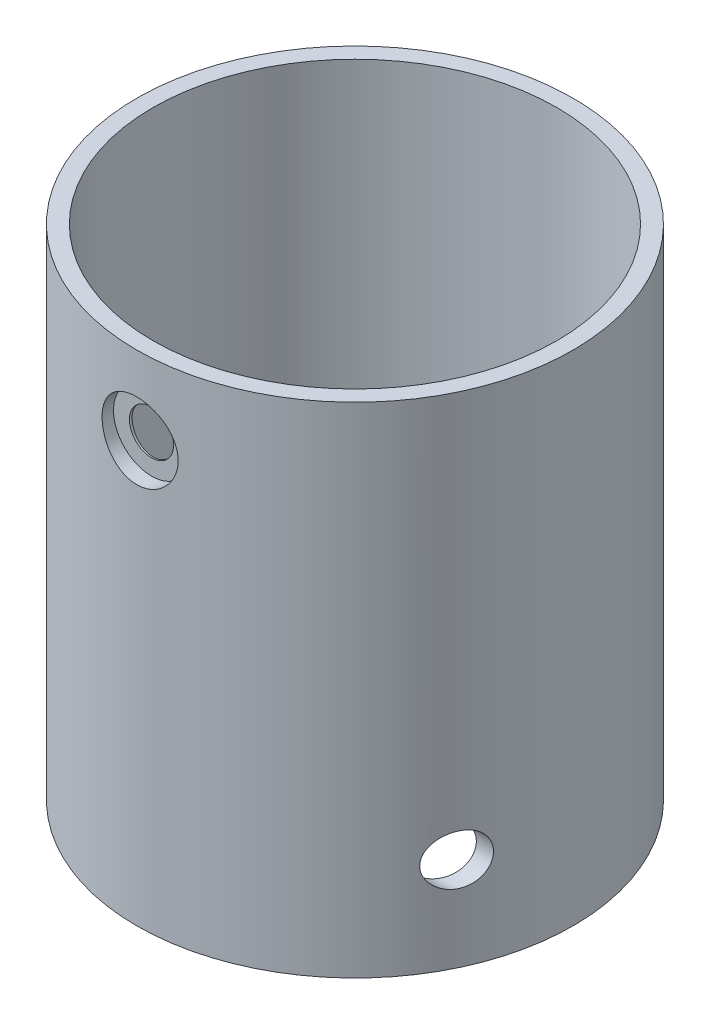
SolidWorks part; units mm, degrees
ref_plane "Front Plane" through (0, 0, 0) normal (1, 0, 0) x (0, 1, 0)
ref_plane "Top Plane" through (0, 0, 0) normal (0, 0, 1) x (0, 1, 0)
ref_plane "Right Plane" through (0, 0, 0) normal (0, 1, 0) x (-1, 0, 0)
sketch "Sketch1" plane through (0, 0, 0) normal (0, 1, 0) x (-1, 0, 0)
  circle A0 centre (0, 0) radius 22.225
  circle A1 centre (0, 0) radius 20.574
  point P4 (-22.225, 0)
  point P5 (-20.574, 0)
  dimension "D1" = 44.45
  dimension "D2" = 1.651
extrude "Boss-Extrude1" add sketch "Sketch1" along normal blind 50.8
sketch "Sketch2" plane through (0, 0, 0) normal (1, 0, 0) x (0, 1, 0)
  circle A0 centre (9.525, 9.525) radius 2.54
  point P2 (7.4057, 3.6887)
  dimension "D1" = 5.08
  dimension "D2" = 9.525
  dimension "D3" = 9.525
extrude "Cut-Extrude1" cut sketch "Sketch2" along normal blind 50.8
ref_plane "Plane1" through (0, 0, 22.225) normal (0, 0, 1) x (1, 0, 0)
sketch "Sketch3" plane through (0, 0, 22.225) normal (0, 0, 1) x (1, 0, 0)
  line L0 (20.574, 50.8) -> (-20.574, 50.8) construction
  line L1 (22.225, 50.8) -> (-22.225, 50.8) construction
  circle A0 centre (0, 42.8) radius 3.875
  circle A1 centre (0, 42.8) radius 2.25
  point P6 (0, 50.8)
  dimension "D1" = 7.75
  dimension "D3" = 4.5
  dimension "D2" = 8
extrude "Cut-Extrude2" cut sketch "Sketch3" against normal blind 1.5
extrude "Cut-Extrude3" cut sketch "Sketch3<2>" against normal blind 16.17 contours A1 region at (0, 42.8, 22.225)
sketch "Sketch3<2>" plane through (0, 0, 22.225) normal (0, 0, 1) x (1, 0, 0) same geometry as "Sketch3"
